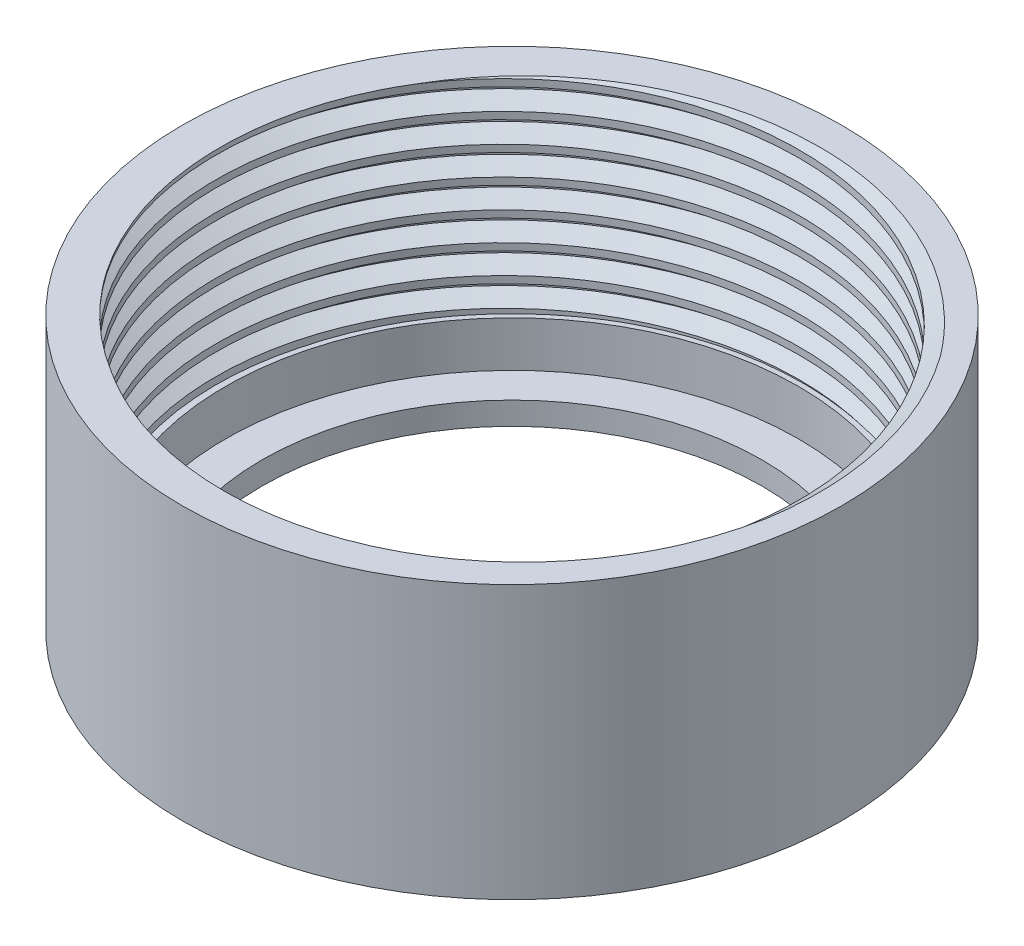
SolidWorks part; units mm, degrees
ref_plane "前视基准面" through (0, 0, 0) normal (0, 0, 1) x (1, 0, 0)
ref_plane "上视基准面" through (0, 0, 0) normal (0, 1, 0) x (1, 0, 0)
ref_plane "右视基准面" through (0, 0, 0) normal (1, 0, 0) x (0, 0, -1)
other "Configuration Table"
sketch "草图1" plane through (0, 0, 0) normal (0, 1, 0) x (1, 0, 0)
  circle A0 centre (0, 0) radius 14.5
  circle A1 centre (0, 0) radius 11
  dimension "D1" = 22
  dimension "D2" = 29
extrude "凸台-拉伸1" add sketch "草图1" along normal blind 1
sketch "草图2" plane through (0, 1, 0) normal (0, 1, 0) x (1, 0, 0)
  circle A0 centre (0, 0) radius 14.5 construction
  circle A1 centre (0, 0) radius 14.5
  circle A2 centre (0, 0) radius 12.6
  dimension "D1" = 25.2
extrude "凸台-拉伸2" add sketch "草图2" along normal blind 11
sketch "草图3" plane through (0, 12, 0) normal (0, 1, 0) x (1, 0, 0)
  circle A0 centre (0, 0) radius 13.5
  dimension "D1" = 27
extrude "切除-拉伸1" cut sketch "草图3" against normal offset from surface (9 mm away) 2 up to face at (0, 1, 11)
thread "螺纹线1" pitch 1.25 method extrude trim with start face yes trim with end face yes profile "螺纹线轮廓1" start angle 0, offset 3, length 0, pitch 1.25, diameter 27
ref_plane "基准面1" through (-13.5, 15, 0) normal (0, 0, 1) x (-1, 0, 0)
sketch "螺纹线轮廓1" plane through (-13.5, 15, 0) normal (0, 0, 1) x (-1, 0, 0)
  line L0 (0, 0) -> (0, 1.25) construction
  line L11 (0, 0) -> (0, 1.0937)
  line L12 (0, 1.0937) -> (-0.6766, 0.7031)
  line L13 (-0.6766, 0.7031) -> (-0.6766, 0.3906)
  line L15 (-0.6766, 0.3906) -> (0, 0)
  line L17 (-0.6766, 0.5469) -> (0, 0.5469) construction
  point P2 (0, 0)
  dimension "Pitch" = 1.25
  dimension "Profile_Angle" = 60
  dimension "Profile_Land" = 0.3125
  dimension "Profile_Height" = 0.6766
